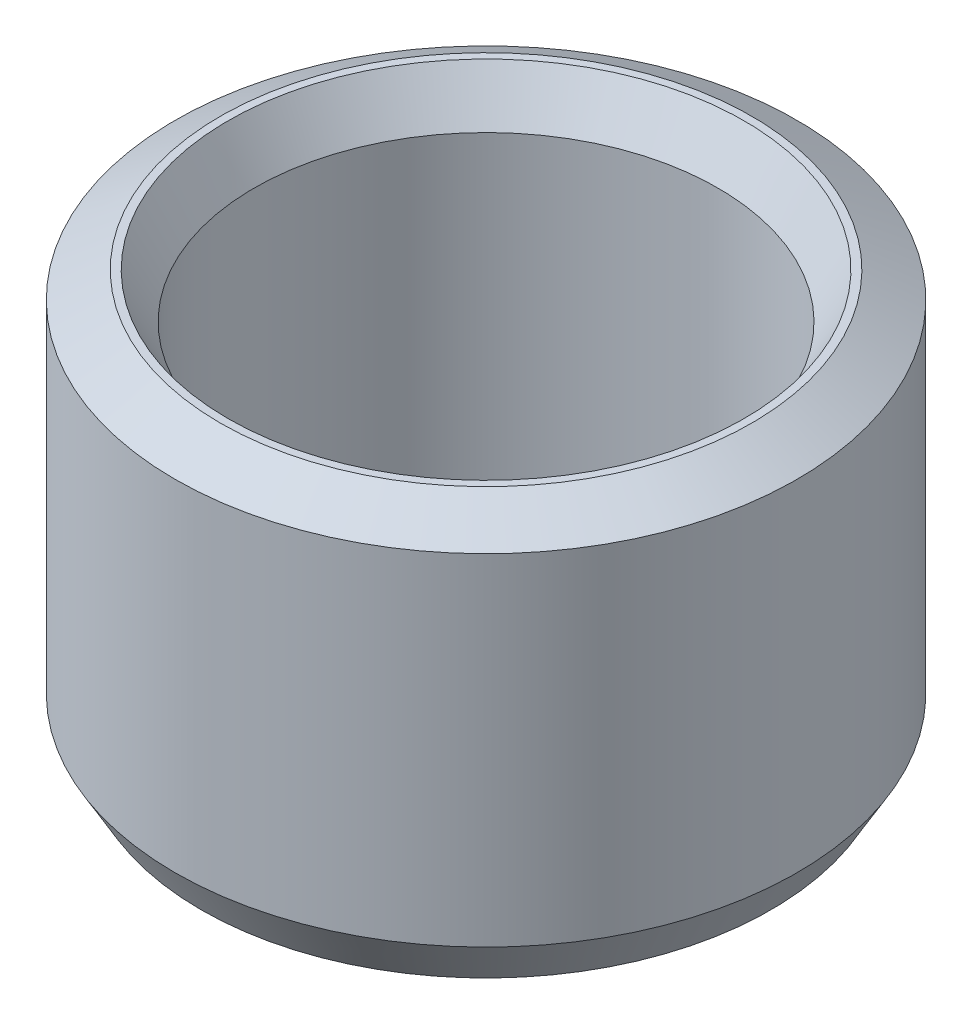
SolidWorks part; units mm, degrees
ref_plane "Front Plane" through (0, 0, 0) normal (0, 0, 1) x (1, 0, 0)
ref_plane "Top Plane" through (0, 0, 0) normal (0, 1, 0) x (1, 0, 0)
ref_plane "Right Plane" through (0, 0, 0) normal (1, 0, 0) x (0, 0, -1)
sketch "Sketch1" plane through (0, 0, 0) normal (0, 1, 0) x (1, 0, 0)
  circle A0 centre (0, 0) radius 30
  dimension "SLEEVE_OD" = 60
extrude "Boss-Extrude1" add sketch "Sketch1" along normal blind 39.7491
sketch "Sketch2" plane through (0, 0, 0) normal (0, 1, 0) x (1, 0, 0)
  circle A0 centre (0, 0) radius 22.3726
  dimension "BORE_D" = 44.7452
extrude "Cut-Extrude1" cut sketch "Sketch2" along normal through all
chamfer "Chamfer1" distance 2.5184 angle 60 4 edges at (0, 39.7491, 22.3726) (0, 0, 22.3726) (0, 0, 30) (0, 39.7491, 30) first distance on face at (0, 39.7491, 22.3726) first distance on face at (0, 0, 22.3726) first distance on face at (0, 39.7491, 30)
